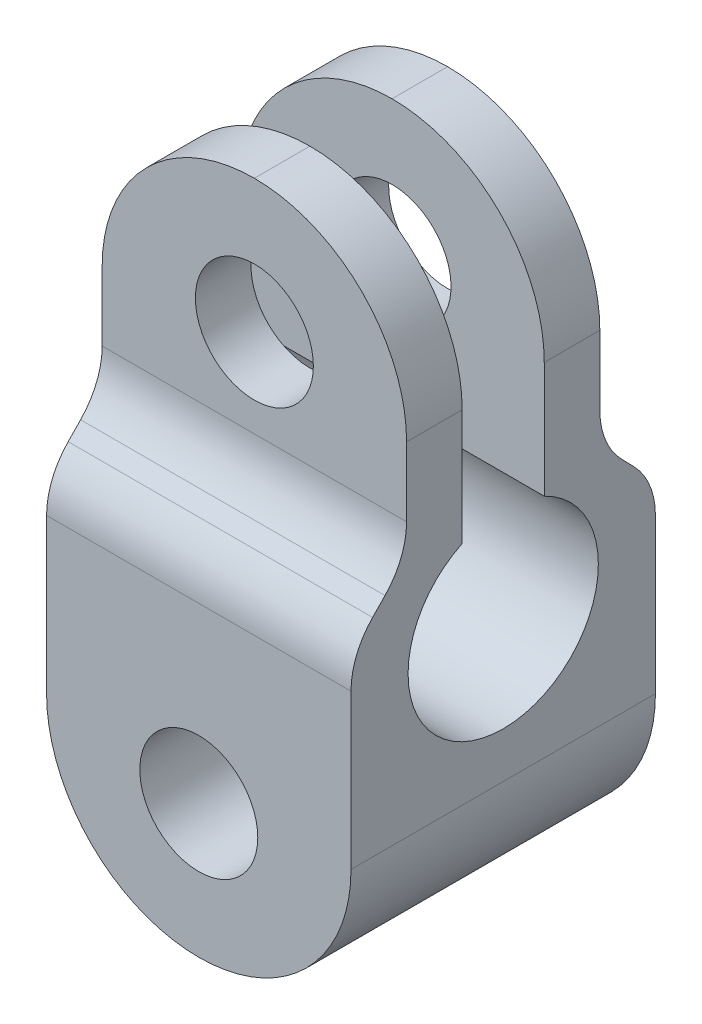
SolidWorks part; units mm, degrees
material "ABS"
ref_plane "前视基准面" through (0, 0, 0) normal (0, 0, 1) x (1, 0, 0)
ref_plane "上视基准面" through (0, 0, 0) normal (0, 1, 0) x (1, 0, 0)
ref_plane "右视基准面" through (0, 0, 0) normal (1, 0, 0) x (0, 0, -1)
sketch "草图1" plane through (0, 0, 0) normal (0, 0, 1) x (1, 0, 0)
  line L0 (0, 0) -> (-8, 0)
  line L1 (-8, 0) -> (-8, 17)
  line L2 (-8, 17) -> (0, 17)
  line L3 (0, 17) -> (0, 0)
extrude "凸台-拉伸2" add sketch "草图1" along normal blind 8
fillet "圆角2" radius 4 4 edges at (0, 0, 4) (-8, 0, 4) (0, 17, 4) (-8, 17, 4)
sketch "草图2" plane through (0, 0, 8) normal (0, 0, 1) x (1, 0, 0)
  circle A0 centre (-4, 13.5) radius 1.55
  circle A1 centre (-4, 3.5) radius 1.55
  point P7 (-4, 8.5)
extrude "切除-拉伸1" cut sketch "草图2" against normal blind 8
sketch "草图3" plane through (-8, 0, 0) normal (-1, 0, 0) x (0, 0, 1)
  circle A0 centre (4, 7.7) radius 2.5
extrude "切除-拉伸2" cut sketch "草图3" against normal blind 8
sketch "草图4" plane through (-8, 0, 0) normal (-1, 0, 0) x (0, 0, 1)
  line L0 (2.9215, 9.9554) -> (2.9215, 17)
  line L2 (0, 17) -> (8, 17) construction
  line L3 (2.9215, 17) -> (5.0785, 17)
  line L4 (5.0785, 9.9554) -> (5.0785, 17)
  line L5 (2.9215, 9.9554) -> (2.9215, 9.7866)
  line L6 (5.0785, 9.9554) -> (5.0785, 9.7866)
  circle A0 centre (4, 7.7) radius 2.5 construction
  arc A1 (2.9215, 9.7866) -> (5.0785, 9.7866) centre (4, 7.5501) cw
extrude "切除-拉伸4" cut sketch "草图4" against normal blind 8
sketch "草图5" plane through (-8, 0, 0) normal (-1, 0, 0) x (0, 0, 1)
  line L0 (4, 7.5) -> (4, 12.9534) construction
  line L2 (0, 13) -> (0, 4) construction
  line L3 (0, 8.8693) -> (1.4608, 10.3693)
  line L4 (1.4608, 10.3693) -> (1.4608, 17)
  line L5 (0, 17) -> (2.9215, 17) construction
  line L6 (1.4608, 17) -> (0, 17)
  line L7 (0, 17) -> (0, 8.8693)
  line L8 (8, 17) -> (8, 8.8693)
  line L9 (6.5392, 17) -> (8, 17)
  line L10 (6.5392, 10.3693) -> (6.5392, 17)
  line L11 (8, 8.8693) -> (6.5392, 10.3693)
extrude "切除-拉伸5" cut sketch "草图5" against normal blind 8
fillet "圆角3" radius 2 4 edges at (-4, 8.8693, 8) (-4, 10.3693, 6.5392) (-4, 8.8693, 0) (-4, 10.3693, 1.4608)
